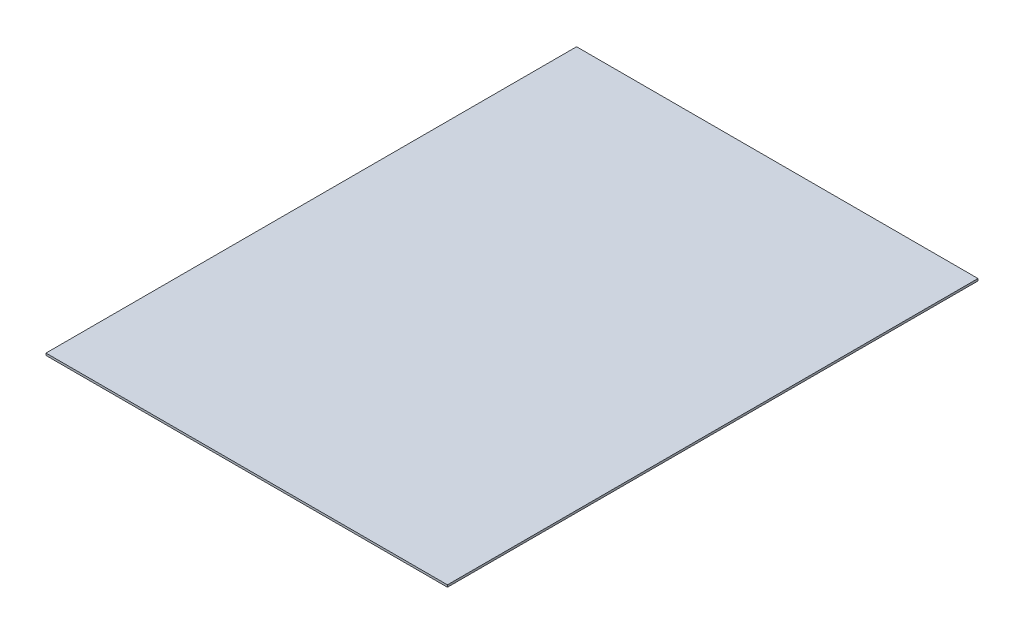
SolidWorks part; units mm, degrees
material "Alumina"
ref_plane "Front Plane" through (0, 0, 0) normal (0, 0, 1) x (1, 0, 0)
ref_plane "Top Plane" through (0, 0, 0) normal (0, 1, 0) x (1, 0, 0)
ref_plane "Right Plane" through (0, 0, 0) normal (1, 0, 0) x (0, 0, -1)
sketch "Sketch3" plane through (0, 0, 0) normal (0, 1, 0) x (1, 0, 0)
  line L1 (-122.5, 161.9) -> (122.5, 161.9)
  line L2 (-122.5, 161.9) -> (-122.5, -161.9)
  line L3 (-122.5, -161.9) -> (122.5, -161.9)
  line L4 (122.5, 161.9) -> (122.5, -161.9)
  line L5 (-122.5, 161.9) -> (122.5, -161.9) construction
  line L6 (-122.5, -161.9) -> (122.5, 161.9) construction
  point P0 (0, 0)
  dimension "D1" = 323.8
  dimension "D2" = 245
extrude "Boss-Extrude1" add sketch "Sketch3" along normal blind 1.2954
